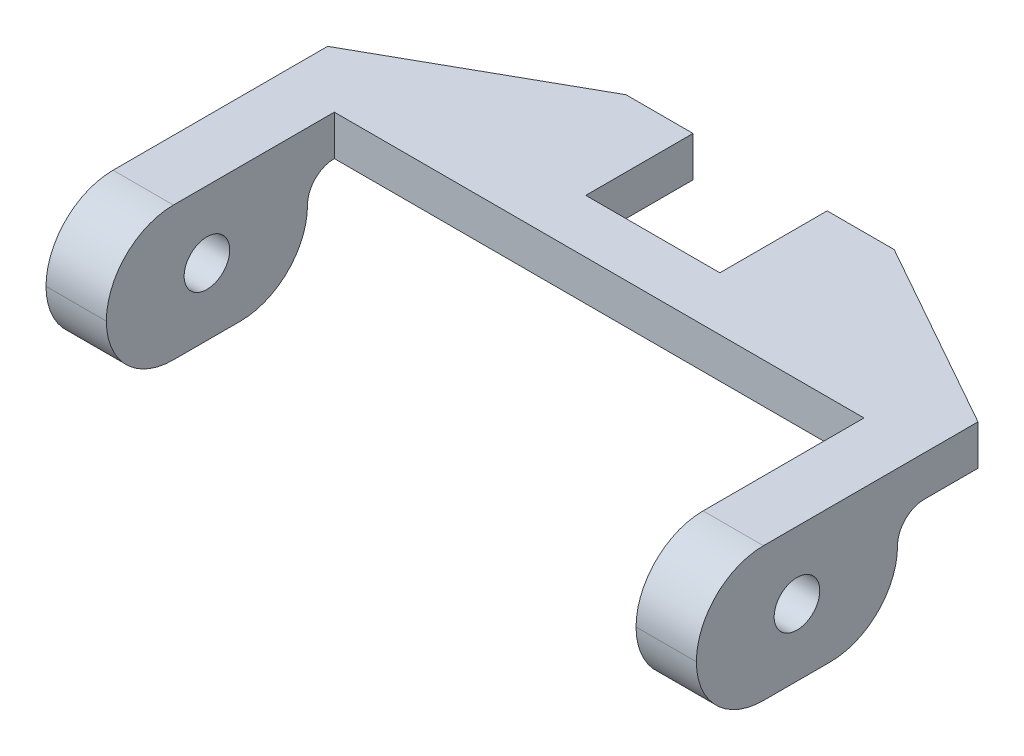
SolidWorks part; units mm, degrees
ref_plane "前视基准面" through (0, 0, 0) normal (0, 0, 1) x (1, 0, 0)
ref_plane "上视基准面" through (0, 0, 0) normal (0, 1, 0) x (1, 0, 0)
ref_plane "右视基准面" through (0, 0, 0) normal (1, 0, 0) x (0, 0, -1)
sketch "Sketch1" plane through (0, 0, 0) normal (0, 1, 0) x (1, 0, 0)
  line L0 (-5, 0) -> (5, 0)
  line L1 (5, 0) -> (5, 8)
  line L2 (5, 8) -> (10, 8)
  line L3 (10, 8) -> (24.25, 0)
  line L4 (-19.75, -4) -> (19.75, -4)
  line L6 (-24.25, -21) -> (-24.25, 0)
  line L7 (0, -4) -> (0, 0) construction
  line L8 (-19.75, -21) -> (-24.25, -21)
  line L9 (-19.75, -4) -> (-19.75, -21)
  line L11 (-10, 8) -> (-24.25, 0)
  line L12 (-5, 8) -> (-10, 8)
  line L13 (19.75, -4) -> (19.75, -21)
  line L14 (19.75, -21) -> (24.25, -21)
  line L15 (24.25, -21) -> (24.25, 0)
  line L16 (-5, 0) -> (-5, 8)
  dimension "D1" = 4
  dimension "D2" = 8
  dimension "D3" = 4.5
  dimension "D4" = 17
  dimension "D5" = 39.5
  dimension "D6" = 5
  dimension "D7" = 10
  dimension "D8" = 21
extrude "Boss-Extrude1" add sketch "Sketch1" along normal blind 3
sketch "Sketch3" plane through (0, 0, 0) normal (0, -1, 0) x (1, 0, 0)
  line L1 (24.25, 21) -> (19.75, 21)
  line L2 (24.25, 21) -> (24.25, 6)
  line L3 (24.25, 6) -> (19.75, 6)
  line L4 (19.75, 21) -> (19.75, 6)
  dimension "D1" = 15
extrude "Boss-Extrude3" add sketch "Sketch3" along normal blind 7
sketch "Sketch4" plane through (24.25, 0, 0) normal (1, 0, 0) x (0, 0, -1)
  line L0 (-21, 3) -> (-6, -7) construction
  circle A0 centre (-13.5, -2) radius 1.7
  dimension "D1" = 3.4
extrude "Cut-Extrude1" cut sketch "Sketch4" against normal up to next
mirror "Mirror2" about plane through (0, 0, 0) normal (1, 0, 0) of "Boss-Extrude3", "Cut-Extrude1"
fillet "Fillet2" radius 5 6 edges at (22, -7, 6) (22, -7, 21) (22, 3, 21) (-22, -7, 6) (-22, -7, 21) (-22, 3, 21)
fillet "Fillet3" radius 2 2 edges at (-22, 0, 6)
